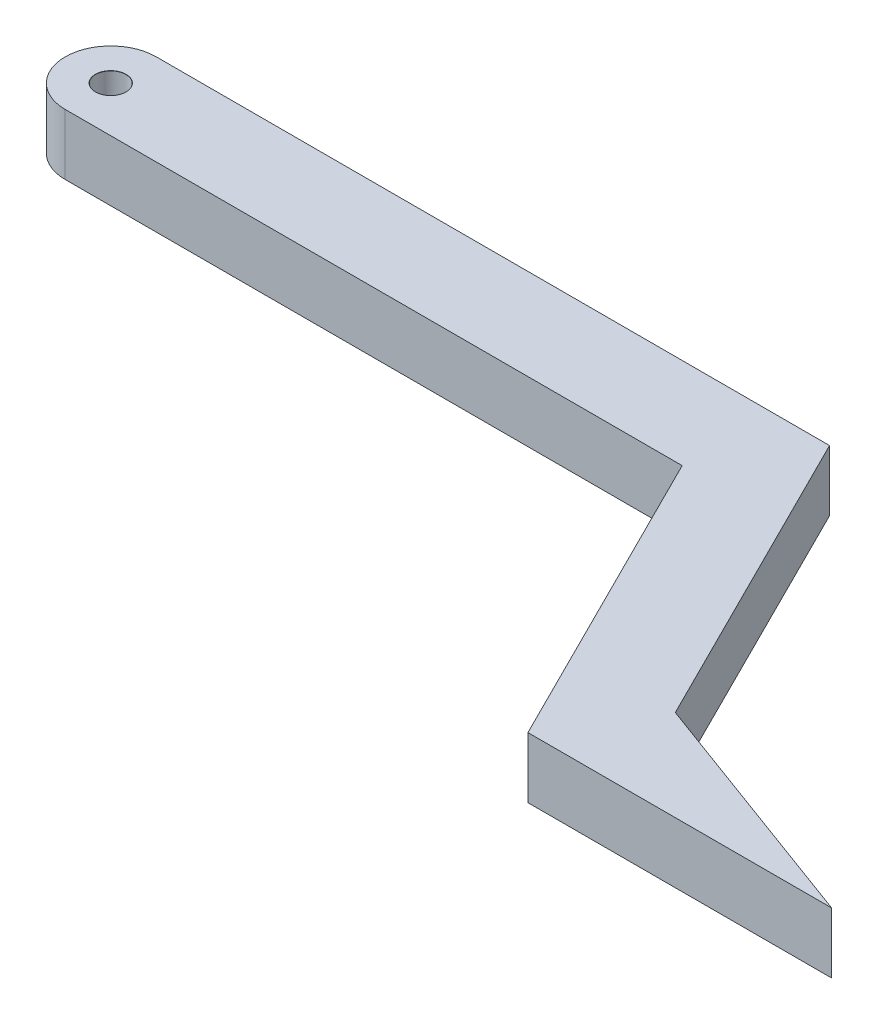
SolidWorks part; units mm, degrees
ref_plane "Front Plane" through (0, 0, 0) normal (0, 0, 1) x (1, 0, 0)
ref_plane "Top Plane" through (0, 0, 0) normal (0, 1, 0) x (1, 0, 0)
ref_plane "Right Plane" through (0, 0, 0) normal (1, 0, 0) x (0, 0, -1)
sketch "Sketch1" plane through (0, 0, 0) normal (0, 1, 0) x (1, 0, 0)
  line L0 (0, 0) -> (101.6, 0)
  line L1 (-55, 0) -> (55, 0) construction
  line L2 (101.6, 0) -> (126.9703, -50.7703)
  line L3 (126.9703, -50.7703) -> (176.9703, -50.7703)
  line L4 (0, 15) -> (110.8729, 15)
  line L5 (110.8729, 15) -> (136.2432, -35.7703)
  line L6 (0, 0) -> (0, 15)
  line L7 (176.9703, -50.7703) -> (136.2432, -35.7703)
  line L9 (136.2432, -35.7703) -> (176.9703, -35.7703) construction
  dimension "D1" = 15
extrude "Boss-Extrude1" add sketch "Sketch1" along normal blind 10
sketch "Sketch2" plane through (0, 10, 0) normal (0, 1, 0) x (1, 0, 0)
  line L3 (0, -55) -> (0, 55) construction
  line L4 (0, 15) -> (0, 0)
  arc A0 (0, 15) -> (0, 0) centre (0, 7.5) ccw
  point P0 (0, 7.5)
extrude "Boss-Extrude2" add sketch "Sketch2" against normal blind 10
sketch "Sketch4" plane through (0, 10, 0) normal (0, 1, 0) x (1, 0, 0)
  line L0 (0, 15) -> (0, 0) construction
  point P0 (0, 7.5)
hole_wizard "Ø5.0mm Dowel Hole2" positions "Sketch4" profile "Sketch5" hole size "Ø5.0" standard "ANSI Metric" end condition through all
sketch "Sketch5" plane through (0, 10, -7.5) normal (1, 0, 0) x (0, 0, 1)
  line L0 (0, 0) -> (0, 10)
  line L1 (0, 10) -> (2.5, 10)
  line L2 (2.5, 10) -> (2.5, 0.025)
  line L3 (2.5, 0.025) -> (2.525, 0)
  line L5 (2.525, 0) -> (0, 0)
  line L6 (-2.5, 0.025) -> (-2.525, 0) construction
  line L11 (0, -6.35) -> (0, 107.95) construction
  dimension "Thru Hole Dia." = 5
  dimension "Thru Hole Depth" = 10
  dimension "Near C'Sink Dia." = 5.05
  dimension "Near C'Sink Angle" = 90
